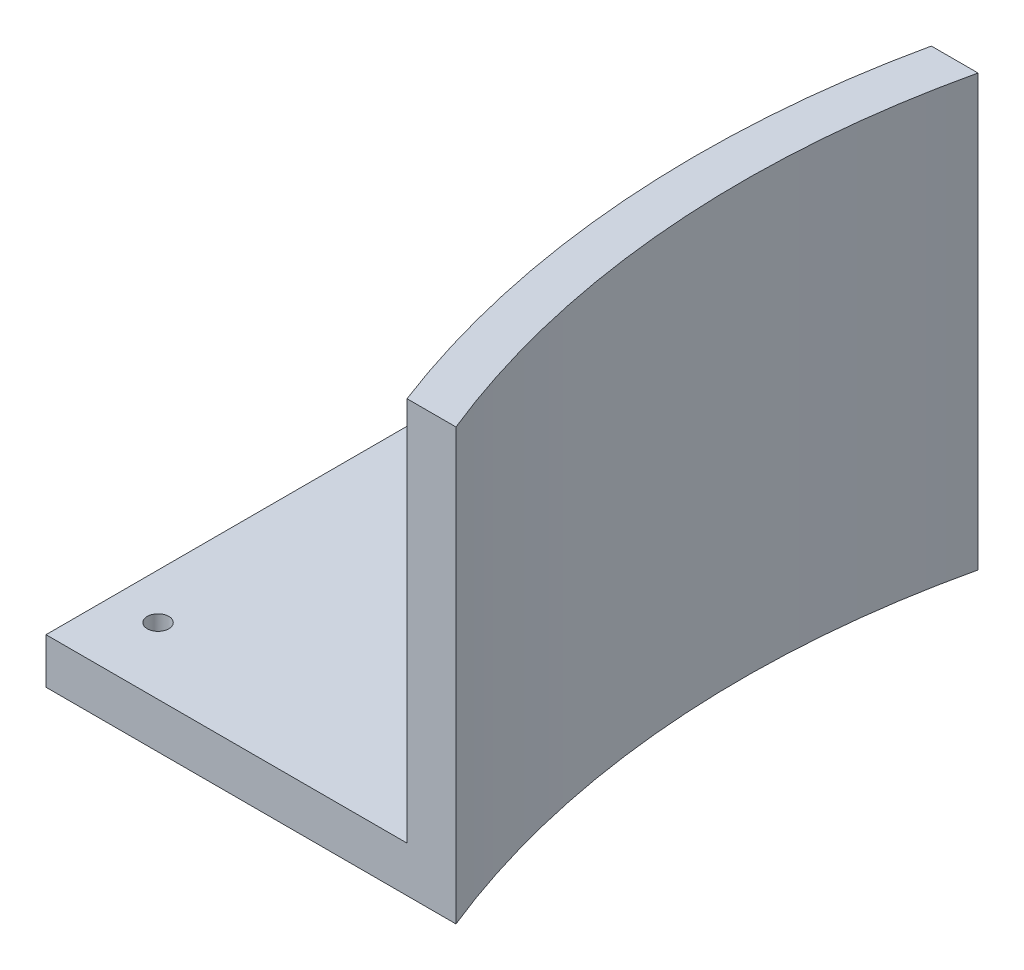
SolidWorks part; units mm, degrees
ref_plane "Front Plane" through (0, 0, 0) normal (0, 0, 1) x (1, 0, 0)
ref_plane "Top Plane" through (0, 0, 0) normal (0, 1, 0) x (1, 0, 0)
ref_plane "Right Plane" through (0, 0, 0) normal (1, 0, 0) x (0, 0, -1)
sketch "Sketch1" plane through (0, 0, 0) normal (0, 1, 0) x (1, 0, 0)
  line L0 (50.8, 79.121) -> (0, 79.121)
  line L1 (0, 79.121) -> (0, 0)
  line L2 (0, 0) -> (57.15, 0)
  arc A1 (50.8, 79.121) -> (57.15, 0) centre (179.5475, 49.6385) ccw
  dimension "D2" = 264.16
  dimension "D3" = 79.121
  dimension "D4" = 57.15
extrude "Boss-Extrude1" add sketch "Sketch1" along normal blind 60
sketch "Sketch3" plane through (0, 0, 0) normal (0, 1, 0) x (1, 0, 0)
  line L0 (51.2655, -2.3865) -> (0, 0)
  line L2 (0, 0) -> (0, 79.121)
  line L3 (0, 79.121) -> (44.2935, 79.121)
  line L5 (50.8, 79.121) -> (0, 79.121) construction
  arc A3 (44.6102, 80.5384) -> (51.2655, -2.3865) centre (179.5475, 49.6385) ccw
  arc A4 (44.2935, 79.121) -> (51.2655, -2.3865) centre (179.5475, 49.6385) ccw
  dimension "D1" = 6.35
extrude "Cut-Extrude1" cut sketch "Sketch3" against normal offset from surface (53.65 mm away) 6.35 from surface up to face at (25.4665, 0, -39.4384) starting at face at (25.4665, 60, -39.4384)
sketch "Sketch4" plane through (0, 6.35, 0) normal (0, 1, 0) x (1, 0, 0)
  line L0 (44.2935, 79.121) -> (0, 79.121) construction
  line L1 (0, 79.121) -> (0, 0) construction
  circle A0 centre (6.35, 72.771) radius 1.5
  circle A1 centre (25.4, 72.771) radius 1.5
  circle A3 centre (6.35, 9.271) radius 1.5
  circle A4 centre (25.4, 9.271) radius 1.5 [skipped]
  dimension "D1" = 3
  dimension "D2" = 6.35
  dimension "D3" = 6.35
  dimension "D5" = 2
extrude "Cut-Extrude2" cut sketch "Sketch4" against normal through all
equation "\"tightTol\"= 0.005in"
equation "\"normTol\"= 0.01in"
equation "\"looseTol\"= 0.02in"
equation "\"D3@Sketch1\"=3.125000in-\"normTol\""
equation "\"D1@Sketch4\"=3mm"
equation "\"D1@Boss-Extrude1\"=60mm"
